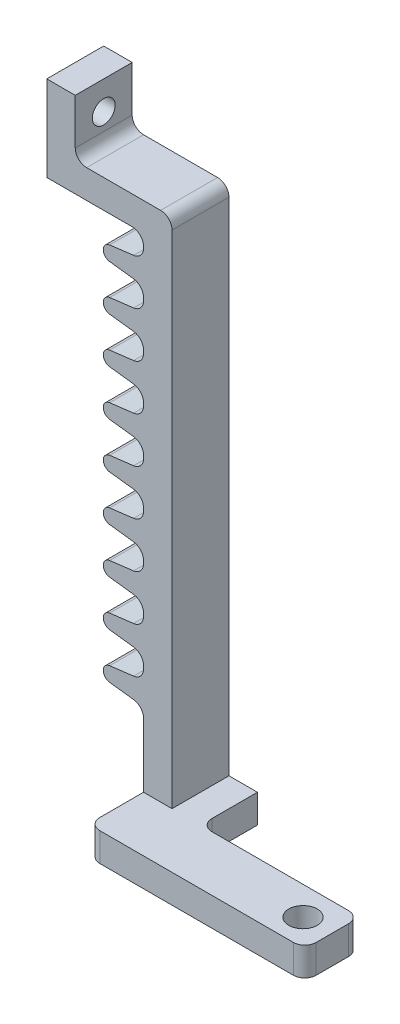
SolidWorks part; units mm, degrees
ref_plane "Front Plane" through (0, 0, 0) normal (0, 0, 1) x (1, 0, 0)
ref_plane "Top Plane" through (0, 0, 0) normal (0, 1, 0) x (1, 0, 0)
ref_plane "Right Plane" through (0, 0, 0) normal (1, 0, 0) x (0, 0, -1)
sketch "Sketch1" plane through (0, 0, 0) normal (0, 1, 0) x (1, 0, 0)
  line L0 (-8, 56.9408) -> (-8, 59.7408)
  line L1 (0, 57.5) -> (0, -57.5) construction
  line L2 (8, 56.9408) -> (8, 59.7408)
  line L3 (-6, 61.7408) -> (6, 61.7408)
  line L4 (39.4147, 47.8999) -> (47.8999, 39.4147)
  line L9 (34.6063, 45.9201) -> (36.5862, 47.8999)
  line L10 (45.9201, 34.6063) -> (47.8999, 36.5862)
  line L15 (61.7408, 6) -> (61.7408, -6)
  line L16 (56.9408, 8) -> (59.7408, 8)
  line L17 (56.9408, -8) -> (59.7408, -8)
  line L22 (47.8999, -39.4147) -> (39.4147, -47.8999)
  line L23 (45.9201, -34.6063) -> (47.8999, -36.5862)
  line L24 (34.6063, -45.9201) -> (36.5862, -47.8999)
  line L29 (6, -61.7408) -> (-6, -61.7408)
  line L30 (8, -56.9408) -> (8, -59.7408)
  line L31 (-8, -56.9408) -> (-8, -59.7408)
  line L36 (-39.4147, -47.8999) -> (-47.8999, -39.4147)
  line L37 (-34.6063, -45.9201) -> (-36.5862, -47.8999)
  line L38 (-45.9201, -34.6063) -> (-47.8999, -36.5862)
  line L43 (-61.7408, -6) -> (-61.7408, 6)
  line L44 (-56.9408, -8) -> (-59.7408, -8)
  line L45 (-56.9408, 8) -> (-59.7408, 8)
  line L50 (-47.8999, 39.4147) -> (-39.4147, 47.8999)
  line L51 (-45.9201, 34.6063) -> (-47.8999, 36.5862)
  line L52 (-34.6063, 45.9201) -> (-36.5862, 47.8999)
  arc A0 (-8, 56.9408) -> (-34.6063, 45.9201) centre (0, 0) ccw
  arc A1 (6, 61.7408) -> (8, 59.7408) centre (6, 59.7408) cw
  arc A2 (-6, 61.7408) -> (-8, 59.7408) centre (-6, 59.7408) ccw
  arc A3 (39.4147, 47.8999) -> (36.5862, 47.8999) centre (38.0005, 46.4857) ccw
  arc A4 (47.8999, 39.4147) -> (47.8999, 36.5862) centre (46.4857, 38.0005) cw
  arc A5 (61.7408, 6) -> (59.7408, 8) centre (59.7408, 6) ccw
  arc A6 (61.7408, -6) -> (59.7408, -8) centre (59.7408, -6) cw
  arc A7 (47.8999, -39.4147) -> (47.8999, -36.5862) centre (46.4857, -38.0005) ccw
  arc A8 (39.4147, -47.8999) -> (36.5862, -47.8999) centre (38.0005, -46.4857) cw
  arc A9 (6, -61.7408) -> (8, -59.7408) centre (6, -59.7408) ccw
  arc A10 (-6, -61.7408) -> (-8, -59.7408) centre (-6, -59.7408) cw
  arc A11 (-39.4147, -47.8999) -> (-36.5862, -47.8999) centre (-38.0005, -46.4857) ccw
  arc A12 (-47.8999, -39.4147) -> (-47.8999, -36.5862) centre (-46.4857, -38.0005) cw
  arc A13 (-61.7408, -6) -> (-59.7408, -8) centre (-59.7408, -6) ccw
  arc A14 (-61.7408, 6) -> (-59.7408, 8) centre (-59.7408, 6) cw
  arc A15 (-47.8999, 39.4147) -> (-47.8999, 36.5862) centre (-46.4857, 38.0005) ccw
  arc A16 (-39.4147, 47.8999) -> (-36.5862, 47.8999) centre (-38.0005, 46.4857) cw
  arc A17 (-45.9201, 34.6063) -> (-56.9408, 8) centre (0, 0) ccw
  arc A18 (-56.9408, -8) -> (-45.9201, -34.6063) centre (0, 0) ccw
  arc A19 (34.6063, 45.9201) -> (8, 56.9408) centre (0, 0) ccw
  arc A20 (-34.6063, -45.9201) -> (-8, -56.9408) centre (0, 0) ccw
  arc A21 (8, -56.9408) -> (34.6063, -45.9201) centre (0, 0) ccw
  arc A22 (45.9201, -34.6063) -> (56.9408, -8) centre (0, 0) ccw
  arc A23 (56.9408, 8) -> (45.9201, 34.6063) centre (0, 0) ccw
  point P11 (8, 61.7408)
  point P14 (-8, 61.7408)
  point P17 (-8, 58.3408)
  point P98 (0, 0)
  dimension "D1" = 115
  dimension "D2" = 2
  dimension "D3" = 16
  dimension "D4" = 2.8
  dimension "D7" = 8
extrude "Boss-Extrude1" add sketch "Sketch1" along normal blind 7
sketch "Sketch2" plane through (0, 7, 0) normal (0, 1, 0) x (1, 0, 0)
  line L0 (-57.5, 0) -> (57.5, 0) construction
  line L1 (0, 0) -> (0, 10) construction
  line L7 (17, 5) -> (22, 5)
  line L14 (0, 10) -> (29.7122, 10) construction
  line L15 (0, 10) -> (-19.5, 10) construction
  line L17 (17, 5) -> (17, 15)
  line L18 (-22, 15) -> (-17, 15)
  line L19 (-22, 15) -> (-22, 5)
  line L20 (-22, 5) -> (-17, 5)
  line L21 (-17, 15) -> (-17, 5)
  line L22 (-22, 15) -> (-17, 5) construction
  line L23 (-22, 5) -> (-17, 15) construction
  line L24 (17, 15) -> (22, 15)
  line L25 (22, 5) -> (22, 15)
  line L26 (17, 5) -> (22, 15) construction
  line L27 (17, 15) -> (22, 5) construction
  circle A0 centre (0, 0) radius 57.5 construction
  point P8 (19.5, 10)
  dimension "D1" = 10
  dimension "D2" = 17
  dimension "D3" = 17
  dimension "D4" = 10
  dimension "D5" = 5
  dimension "D6" = 10
  dimension "D7" = 5
extrude "Boss-Extrude2" add sketch "Sketch2" along normal blind 95
sketch "Sketch15" plane through (0, 0, 0) normal (0, -1, 0) x (1, 0, 0)
  circle A0 centre (0, 0) radius 3.5
  dimension "D1" = 7
extrude "Cut-Extrude3" cut sketch "Sketch15" along direction (0, 1, 0) on the side against the normal up to surface (7 mm away) contours A0 up to face at (0, 7, 0)
sketch "Sketch16" plane through (0, 0, 0) normal (0, -1, 0) x (1, 0, 0)
  line L1 (-6, 59.8) -> (6, 59.8)
  line L2 (-6, 59.8) -> (-6, 57.5)
  line L3 (-6, 57.5) -> (6, 57.5)
  line L4 (6, 59.8) -> (6, 57.5)
  point P5 (0, 57.5)
  dimension "D1" = 2.3
  dimension "D2" = 12
  dimension "D3" = 57.5
sketch "Sketch17" plane through (0, 7, 0) normal (0, 1, 0) x (1, 0, 0)
  line L0 (-6, -57.5) -> (6, -57.5) construction
  line L1 (-6, -57.5) -> (6, -57.5)
  line L2 (-6, -57.5) -> (-6, -60.5)
  line L3 (-6, -60.5) -> (6, -60.5)
  line L4 (6, -60.5) -> (6, -57.5)
  dimension "D1" = 3
ref_axis "Axis1" through (0, 107.1, 0) along (0, -1, 0)
sketch "Sketch18" plane through (-17, 0, 0) normal (1, 0, 0) x (0, 0, -1)
  line L0 (15, 102) -> (15, 7) construction
  line L1 (5, 102) -> (15, 102)
  line L2 (5, 102) -> (5, 97)
  line L3 (5, 97) -> (15, 97)
  line L4 (15, 102) -> (15, 97)
  dimension "D1" = 5
extrude "Boss-Extrude3" add sketch "Sketch18" along normal up to surface (34 mm away) up to face at (17, 54.5, -10)
sketch "Sketch19" plane through (0, 0, -15) normal (0, 0, -1) x (-1, 0, 0)
  line L0 (-17, 93) -> (-11.0447, 92.2688)
  line L1 (-17, 97) -> (-17, 7) construction
  line L4 (-11, 91) -> (-19.8185, 91) construction
  line L5 (-17, 89) -> (-11.0447, 89.7312)
  line L6 (-17, 93) -> (-17, 89)
  arc A1 (-11.0447, 92.2688) -> (-11.0447, 89.7312) centre (-11.2005, 91) cw
  dimension "D1" = 6
  dimension "D4" = 4
  dimension "D2" = 7
  dimension "D3" = 4
extrude "Boss-Extrude4" add sketch "Sketch19" against normal blind 10
fillet "Fillet1" radius 2 2 edges at (17, 93, -10) (17, 89, -10)
fillet "Fillet2" radius 2 4 edges at (-22, 102, -10) (22, 102, -10) (-17, 97, -10) (17, 97, -10)
pattern_linear "LPattern2" count 9 spacing 8 along (0, -1, 0) of "Fillet1", "Boss-Extrude4"
sketch "Sketch20" plane through (0, 7, 0) normal (0, 1, 0) x (1, 0, 0)
  line L0 (0, 0) -> (0, 50) construction
  circle A0 centre (0, 50) radius 2.5
  dimension "D2" = 5
  dimension "D1" = 50
extrude "Cut-Extrude4" cut sketch "Sketch20" against normal blind 10
pattern_circular "CirPattern2" count 4 over 360 about axis through (0, 107.1, 0) along (0, -1, 0) of "Cut-Extrude4"
sketch "Sketch22" plane through (0, 0, 0) normal (1, 0, 0) x (0, 0, -1)
  line L1 (67.7074, 106.8544) -> (-67.9721, 106.8544)
  line L2 (67.7074, 106.8544) -> (67.7074, -6.1109)
  line L3 (67.7074, -6.1109) -> (-67.9721, -6.1109)
  line L4 (-67.9721, 106.8544) -> (-67.9721, -6.1109)
  dimension "D1" = 67.7074
  dimension "D2" = 112.9653
  dimension "D3" = 106.8544
  dimension "D4" = 67.9721
extrude "Cut-Extrude5" cut sketch "Sketch22" against normal up to surface (61.7408 mm away) up to face at (-61.7408, 3.5, 0)
sketch "Sketch23" plane through (0, 7, 0) normal (0, 1, 0) x (1, 0, 0)
  line L1 (17, 5) -> (53, 5)
  line L2 (17, 5) -> (17, -2.6871)
  line L3 (19, -4.6871) -> (53, -4.6871)
  line L4 (55, 3) -> (55, -2.6871)
  line L29 (6, 61.7408) -> (0, 61.7408)
  line L30 (0, 61.7408) -> (0, 52.5)
  line L35 (0, 47.5) -> (0, 3.5)
  line L36 (0, -3.5) -> (0, -47.5)
  line L37 (0, -52.5) -> (0, -61.7408)
  line L42 (0, -61.7408) -> (6, -61.7408)
  line L43 (8, -59.7408) -> (8, -56.9408)
  line L44 (34.6063, -45.9201) -> (36.5862, -47.8999)
  line L45 (39.4147, -47.8999) -> (47.8999, -39.4147)
  line L46 (47.8999, -36.5862) -> (45.9201, -34.6063)
  line L47 (56.9408, -8) -> (59.7408, -8)
  line L48 (61.7408, -6) -> (61.7408, 6)
  line L49 (59.7408, 8) -> (56.9408, 8)
  line L50 (45.9201, 34.6063) -> (47.8999, 36.5862)
  line L51 (47.8999, 39.4147) -> (39.4147, 47.8999)
  line L52 (36.5862, 47.8999) -> (34.6063, 45.9201)
  line L53 (8, 56.9408) -> (8, 59.7408)
  line L54 (6, 61.7408) -> (0, 61.7408)
  line L55 (0, 61.7408) -> (0, 52.5)
  line L60 (0, 47.5) -> (0, 3.5)
  line L61 (0, -3.5) -> (0, -47.5)
  line L62 (0, -52.5) -> (0, -61.7408)
  line L67 (0, -61.7408) -> (6, -61.7408)
  line L68 (8, -59.7408) -> (8, -56.9408)
  line L69 (34.6063, -45.9201) -> (36.5862, -47.8999)
  line L70 (39.4147, -47.8999) -> (47.8999, -39.4147)
  line L71 (47.8999, -36.5862) -> (45.9201, -34.6063)
  line L72 (56.9408, -8) -> (59.7408, -8)
  line L73 (61.7408, -6) -> (61.7408, 6)
  line L74 (59.7408, 8) -> (56.9408, 8)
  line L75 (45.9201, 34.6063) -> (47.8999, 36.5862)
  line L76 (47.8999, 39.4147) -> (39.4147, 47.8999)
  line L77 (36.5862, 47.8999) -> (34.6063, 45.9201)
  line L78 (8, 56.9408) -> (8, 59.7408)
  arc A0 (19, -4.6871) -> (17, -2.6871) centre (19, -2.6871) cw
  arc A1 (53, -4.6871) -> (55, -2.6871) centre (53, -2.6871) ccw
  arc A2 (55, 3) -> (53, 5) centre (53, 3) ccw
  circle A3 centre (50, 0) radius 2.5 construction
  circle A4 centre (50, 0) radius 2.5
  arc A18 (0, 47.5) -> (0, 52.5) centre (0, 50) ccw
  arc A19 (0, -3.5) -> (0, 3.5) centre (0, 0) ccw
  arc A20 (0, -52.5) -> (0, -47.5) centre (0, -50) ccw
  arc A21 (6, -61.7408) -> (8, -59.7408) centre (6, -59.7408) ccw
  arc A22 (8, -56.9408) -> (34.6063, -45.9201) centre (0, 0) ccw
  arc A23 (36.5862, -47.8999) -> (39.4147, -47.8999) centre (38.0005, -46.4857) ccw
  arc A24 (47.8999, -39.4147) -> (47.8999, -36.5862) centre (46.4857, -38.0005) ccw
  arc A25 (45.9201, -34.6063) -> (56.9408, -8) centre (0, 0) ccw
  arc A26 (59.7408, -8) -> (61.7408, -6) centre (59.7408, -6) ccw
  arc A27 (61.7408, 6) -> (59.7408, 8) centre (59.7408, 6) ccw
  arc A28 (56.9408, 8) -> (45.9201, 34.6063) centre (0, 0) ccw
  arc A29 (47.8999, 36.5862) -> (47.8999, 39.4147) centre (46.4857, 38.0005) ccw
  arc A30 (39.4147, 47.8999) -> (36.5862, 47.8999) centre (38.0005, 46.4857) ccw
  arc A31 (34.6063, 45.9201) -> (8, 56.9408) centre (0, 0) ccw
  arc A32 (8, 59.7408) -> (6, 61.7408) centre (6, 59.7408) ccw
  arc A33 (0, 47.5) -> (0, 52.5) centre (0, 50) ccw
  arc A34 (0, -3.5) -> (0, 3.5) centre (0, 0) ccw
  arc A35 (0, -52.5) -> (0, -47.5) centre (0, -50) ccw
  arc A36 (6, -61.7408) -> (8, -59.7408) centre (6, -59.7408) ccw
  arc A37 (8, -56.9408) -> (34.6063, -45.9201) centre (0, 0) ccw
  arc A38 (36.5862, -47.8999) -> (39.4147, -47.8999) centre (38.0005, -46.4857) ccw
  arc A39 (47.8999, -39.4147) -> (47.8999, -36.5862) centre (46.4857, -38.0005) ccw
  arc A40 (45.9201, -34.6063) -> (56.9408, -8) centre (0, 0) ccw
  arc A41 (59.7408, -8) -> (61.7408, -6) centre (59.7408, -6) ccw
  arc A42 (61.7408, 6) -> (59.7408, 8) centre (59.7408, 6) ccw
  arc A43 (56.9408, 8) -> (45.9201, 34.6063) centre (0, 0) ccw
  arc A44 (47.8999, 36.5862) -> (47.8999, 39.4147) centre (46.4857, 38.0005) ccw
  arc A45 (39.4147, 47.8999) -> (36.5862, 47.8999) centre (38.0005, 46.4857) ccw
  arc A46 (34.6063, 45.9201) -> (8, 56.9408) centre (0, 0) ccw
  arc A47 (8, 59.7408) -> (6, 61.7408) centre (6, 59.7408) ccw
  point P7 (17, -4.6871)
  point P11 (55, -4.6871)
  dimension "D3" = 2
  dimension "D1" = 38
  dimension "D2" = 9.6871
  dimension "D4" = 0
extrude "Boss-Extrude5" add sketch "Sketch23" along normal blind 5 contours L4 A2 L1 L2 A0 L3 A1 A4 region at (35.1593, 7, -0.1762)
sketch "Sketch26" plane through (0, 7, 0) normal (0, 1, 0) x (1, 0, 0)
  line L25 (6, 61.7408) -> (0, 61.7408)
  line L26 (0, 61.7408) -> (0, 52.5)
  line L31 (0, 47.5) -> (0, 3.5)
  line L32 (0, -3.5) -> (0, -47.5)
  line L33 (0, -52.5) -> (0, -61.7408)
  line L38 (0, -61.7408) -> (6, -61.7408)
  line L39 (8, -59.7408) -> (8, -56.9408)
  line L40 (34.6063, -45.9201) -> (36.5862, -47.8999)
  line L41 (39.4147, -47.8999) -> (47.8999, -39.4147)
  line L42 (47.8999, -36.5862) -> (45.9201, -34.6063)
  line L43 (56.9408, -8) -> (59.7408, -8)
  line L44 (61.7408, -6) -> (61.7408, 6)
  line L45 (59.7408, 8) -> (56.9408, 8)
  line L46 (45.9201, 34.6063) -> (47.8999, 36.5862)
  line L47 (47.8999, 39.4147) -> (39.4147, 47.8999)
  line L48 (36.5862, 47.8999) -> (34.6063, 45.9201)
  line L49 (8, 56.9408) -> (8, 59.7408)
  line L50 (6, 61.7408) -> (0, 61.7408)
  line L51 (0, 61.7408) -> (0, 52.5)
  line L56 (0, 47.5) -> (0, 3.5)
  line L57 (0, -3.5) -> (0, -47.5)
  line L58 (0, -52.5) -> (0, -61.7408)
  line L63 (0, -61.7408) -> (6, -61.7408)
  line L64 (8, -59.7408) -> (8, -56.9408)
  line L65 (34.6063, -45.9201) -> (36.5862, -47.8999)
  line L66 (39.4147, -47.8999) -> (47.8999, -39.4147)
  line L67 (47.8999, -36.5862) -> (45.9201, -34.6063)
  line L68 (56.9408, -8) -> (59.7408, -8)
  line L69 (61.7408, -6) -> (61.7408, 6)
  line L70 (59.7408, 8) -> (56.9408, 8)
  line L71 (45.9201, 34.6063) -> (47.8999, 36.5862)
  line L72 (47.8999, 39.4147) -> (39.4147, 47.8999)
  line L73 (36.5862, 47.8999) -> (34.6063, 45.9201)
  line L74 (8, 56.9408) -> (8, 59.7408)
  arc A15 (0, 47.5) -> (0, 52.5) centre (0, 50) ccw
  arc A16 (0, -3.5) -> (0, 3.5) centre (0, 0) ccw
  arc A17 (0, -52.5) -> (0, -47.5) centre (0, -50) ccw
  arc A18 (6, -61.7408) -> (8, -59.7408) centre (6, -59.7408) ccw
  arc A19 (8, -56.9408) -> (34.6063, -45.9201) centre (0, 0) ccw
  arc A20 (36.5862, -47.8999) -> (39.4147, -47.8999) centre (38.0005, -46.4857) ccw
  arc A21 (47.8999, -39.4147) -> (47.8999, -36.5862) centre (46.4857, -38.0005) ccw
  arc A22 (45.9201, -34.6063) -> (56.9408, -8) centre (0, 0) ccw
  arc A23 (59.7408, -8) -> (61.7408, -6) centre (59.7408, -6) ccw
  arc A24 (61.7408, 6) -> (59.7408, 8) centre (59.7408, 6) ccw
  arc A25 (56.9408, 8) -> (45.9201, 34.6063) centre (0, 0) ccw
  arc A26 (47.8999, 36.5862) -> (47.8999, 39.4147) centre (46.4857, 38.0005) ccw
  arc A27 (39.4147, 47.8999) -> (36.5862, 47.8999) centre (38.0005, 46.4857) ccw
  arc A28 (34.6063, 45.9201) -> (8, 56.9408) centre (0, 0) ccw
  arc A29 (8, 59.7408) -> (6, 61.7408) centre (6, 59.7408) ccw
  arc A30 (0, 47.5) -> (0, 52.5) centre (0, 50) ccw
  arc A31 (0, -3.5) -> (0, 3.5) centre (0, 0) ccw
  arc A32 (0, -52.5) -> (0, -47.5) centre (0, -50) ccw
  arc A33 (6, -61.7408) -> (8, -59.7408) centre (6, -59.7408) ccw
  arc A34 (8, -56.9408) -> (34.6063, -45.9201) centre (0, 0) ccw
  arc A35 (36.5862, -47.8999) -> (39.4147, -47.8999) centre (38.0005, -46.4857) ccw
  arc A36 (47.8999, -39.4147) -> (47.8999, -36.5862) centre (46.4857, -38.0005) ccw
  arc A37 (45.9201, -34.6063) -> (56.9408, -8) centre (0, 0) ccw
  arc A38 (59.7408, -8) -> (61.7408, -6) centre (59.7408, -6) ccw
  arc A39 (61.7408, 6) -> (59.7408, 8) centre (59.7408, 6) ccw
  arc A40 (56.9408, 8) -> (45.9201, 34.6063) centre (0, 0) ccw
  arc A41 (47.8999, 36.5862) -> (47.8999, 39.4147) centre (46.4857, 38.0005) ccw
  arc A42 (39.4147, 47.8999) -> (36.5862, 47.8999) centre (38.0005, 46.4857) ccw
  arc A43 (34.6063, 45.9201) -> (8, 56.9408) centre (0, 0) ccw
  arc A44 (8, 59.7408) -> (6, 61.7408) centre (6, 59.7408) ccw
  dimension "D1" = 0
extrude "Cut-Extrude6" cut sketch "Sketch26" against normal blind 10
sketch "Sketch27" plane through (22, 0, 0) normal (1, 0, 0) x (0, 0, -1)
  line L0 (15, 100) -> (15, 7) construction
  line L1 (5, 7) -> (15, 7)
  line L2 (5, 7) -> (5, 12)
  line L3 (5, 12) -> (15, 12)
  line L4 (15, 7) -> (15, 12)
extrude "Boss-Extrude6" add sketch "Sketch27" along normal blind 5
sketch "Sketch28" plane through (0, 102, 0) normal (0, 1, 0) x (1, 0, 0)
  line L0 (0, 5) -> (20, 5) construction
  line L1 (0, 15) -> (5, 15)
  line L2 (0, 15) -> (0, 5)
  line L3 (0, 5) -> (5, 5)
  line L4 (5, 15) -> (5, 5)
  dimension "D1" = 5
extrude "Boss-Extrude7" add sketch "Sketch28" along normal blind 10
sketch "Sketch29" plane through (5, 0, 0) normal (1, 0, 0) x (0, 0, -1)
  line L0 (5, 112) -> (15, 102) construction
  circle A0 centre (10, 107) radius 2
  dimension "D1" = 4
extrude "Cut-Extrude7" cut sketch "Sketch29" against normal up to surface (5 mm away) up to face at (0, 104.5, -10)
fillet "Fillet3" radius 2 2 edges at (27, 9.5, -5) (5, 102, -10)
equation "\"85.00.00mm\"=8500"
